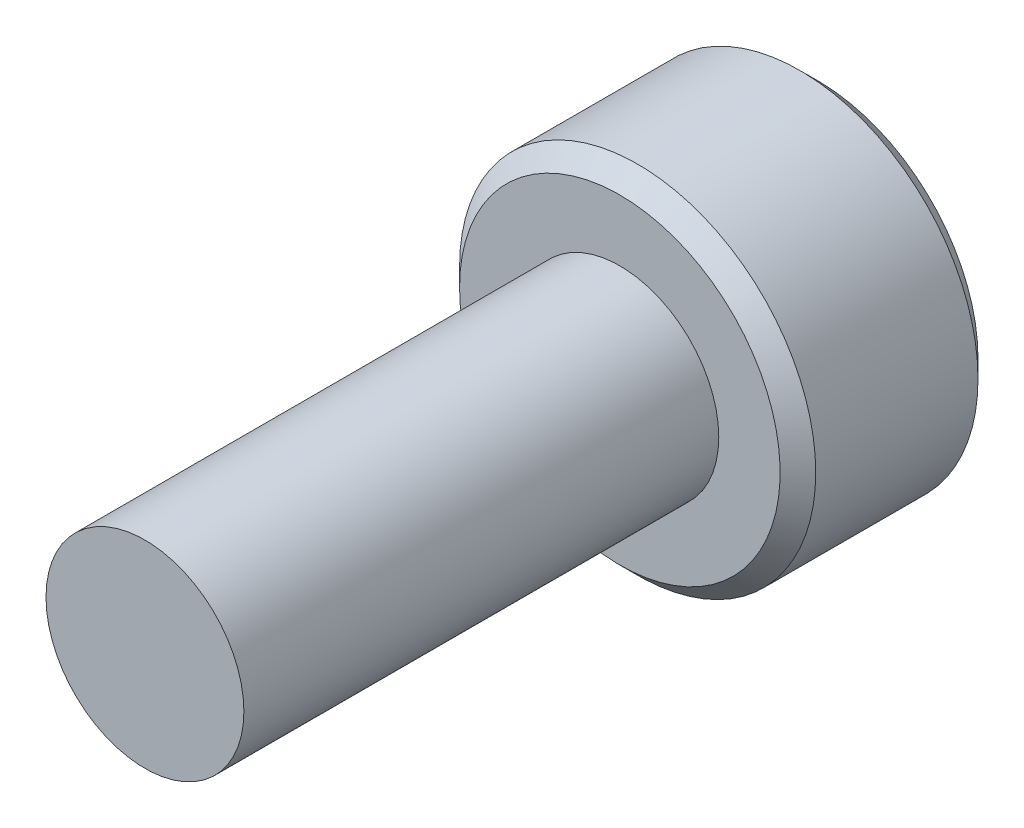
SolidWorks part; units mm, degrees
other "DetailItem1"
ref_plane "Front Plane" through (0, 0, 0) normal (0, 0, 1) x (1, 0, 0)
ref_plane "Top Plane" through (0, 0, 0) normal (0, 1, 0) x (1, 0, 0)
ref_plane "Right Plane" through (0, 0, 0) normal (1, 0, 0) x (0, 0, -1)
sketch "Sketch1" plane through (0, 0, 0) normal (0, 0, 1) x (1, 0, 0)
  circle A0 centre (0, 0) radius 1.25
  dimension "OD" = 2.5
extrude "Extrude1" add sketch "Sketch1" against normal blind 6
sketch "Sketch2" plane through (0, 0, 0) normal (0, 0, 1) x (1, 0, 0)
  circle A0 centre (0, 0) radius 1.25 construction
  circle A1 centre (0, 0) radius 1.25
curve "Helix/Spiral1" pitch 0.45 height 6.45 turns 14.3333 parameters "pitch"=0.45
sketch "Sketch3" plane through (0, 0, 0) normal (1, 0, 0) x (0, 0, -1)
  line L0 (-0.3937, 1.25) -> (-0.225, 0.9577)
  line L1 (-0.225, 0.9577) -> (-0.1688, 0.9577)
  line L2 (-0.1688, 0.9577) -> (0, 1.25)
  line L3 (-0.3937, 1.25) -> (0, 1.25)
  line L4 (-0.1969, 1.25) -> (-0.1969, 0.9577) construction
  line L5 (-0.3094, 1.1039) -> (-0.0844, 1.1039) construction
  line L6 (0, 1.25) -> (0, -1.25) construction
  dimension "D1" = 0.0563
  dimension "D2" = 0.225
  dimension "D3" = 60
sweep "Cut-Sweep1" [suppressed] cut profiles "Sketch3" path "Helix/Spiral1"
sketch "Sketch4" plane through (0, 0, 0) normal (1, 0, 0) x (0, 0, -1)
  line L0 (0.3825, 1.25) -> (0, 0.7037)
  line L1 (0, 0.7037) -> (0, 1.25)
  line L2 (0.3825, 1.25) -> (0, 1.25)
  line L3 (-0.3937, 1.25) -> (0, 1.25) construction
  line L4 (0, 0) -> (7.0209, 0) construction
  dimension "D1" = 55
  dimension "D2" = 0.254
revolve "Cut-Revolve1" [suppressed] cut sketch "Sketch4" angle 360 about L4
sketch "Sketch6" plane through (0, 0, -6) normal (0, 0, -1) x (-1, 0, 0)
  circle A0 centre (0, 0) radius 2.25
  dimension "head dia" = 4.5
extrude "Extrude2" add sketch "Sketch6" along normal blind 2.5
sketch "Sketch7" plane through (0, 0, -8.5) normal (0, 0, -1) x (-1, 0, 0)
  line L1 (0, 1.1547) -> (-1, 0.5774)
  line L2 (-1, 0.5774) -> (-1, -0.5774)
  line L3 (-1, -0.5774) -> (0, -1.1547)
  line L4 (0, -1.1547) -> (1, -0.5774)
  line L5 (1, -0.5774) -> (1, 0.5774)
  line L6 (1, 0.5774) -> (0, 1.1547)
  circle A0 centre (0, 0) radius 1 construction
  dimension "hex dia" = 2
extrude "Cut-Extrude1" cut sketch "Sketch7" against normal blind 1.5
sketch "Sketch8" plane through (0, 0, -8.5) normal (0, 0, -1) x (-1, 0, 0)
  circle A0 centre (0, 0) radius 1.1547
extrude "Cut-Extrude2" cut sketch "Sketch8" against normal through all draft 45
chamfer "Chamfer1" distance 0.225 angle 45 2 edges at (-2.25, 0, -8.5) (-2.25, 0, -6)
sketch "Sketch10" plane through (0, 0, -6) normal (0, 0, 1) x (1, 0, 0)
  circle A1 centre (0, 0) radius 1.25
  circle A2 centre (0, 0) radius 1.25
  dimension "D1" = 0
ref_plane "Plane1" through (0, 0, 0) normal (0, 0, 1) x (1, 0, 0)
extrude "partial thread" [suppressed] add sketch "Sketch10" along normal up to surface (8 mm away) separate body
chamfer "Chamfer2" [suppressed] distance 0.05 angle 45
combine bodies "Combine1" [suppressed] operation type add bodies to combine 107 108
sketch "Sketch9" plane through (0, 0, 0) normal (1, 0, 0) x (0, 0, -1)
  line L0 (0, 1.25) -> (0, -1.25) construction
  line L1 (1.125, 1.25) -> (1.125, -1.25) construction
  dimension "D1" = 1.125
equation "\"D3@Helix/Spiral1\" = \"screw length@Extrude1\"+\"pitch@Helix/Spiral1\""
equation "\"D1@Sketch3\" = \"pitch@Helix/Spiral1\"*.125"
equation "\"D2@Sketch3\" = \"pitch@Helix/Spiral1\"*.5"
equation "\"D1@Cut-Extrude1\" = \"hex dia@Sketch7\"*.75"
equation "\"D1@Chamfer1\" = \"head dia@Sketch6\"*.05"
equation "\"D1@Sketch9\" = \"pitch@Helix/Spiral1\"*2.5"
equation "\"D1@Chamfer2\"=\"OD@Sketch1\"*.02"
